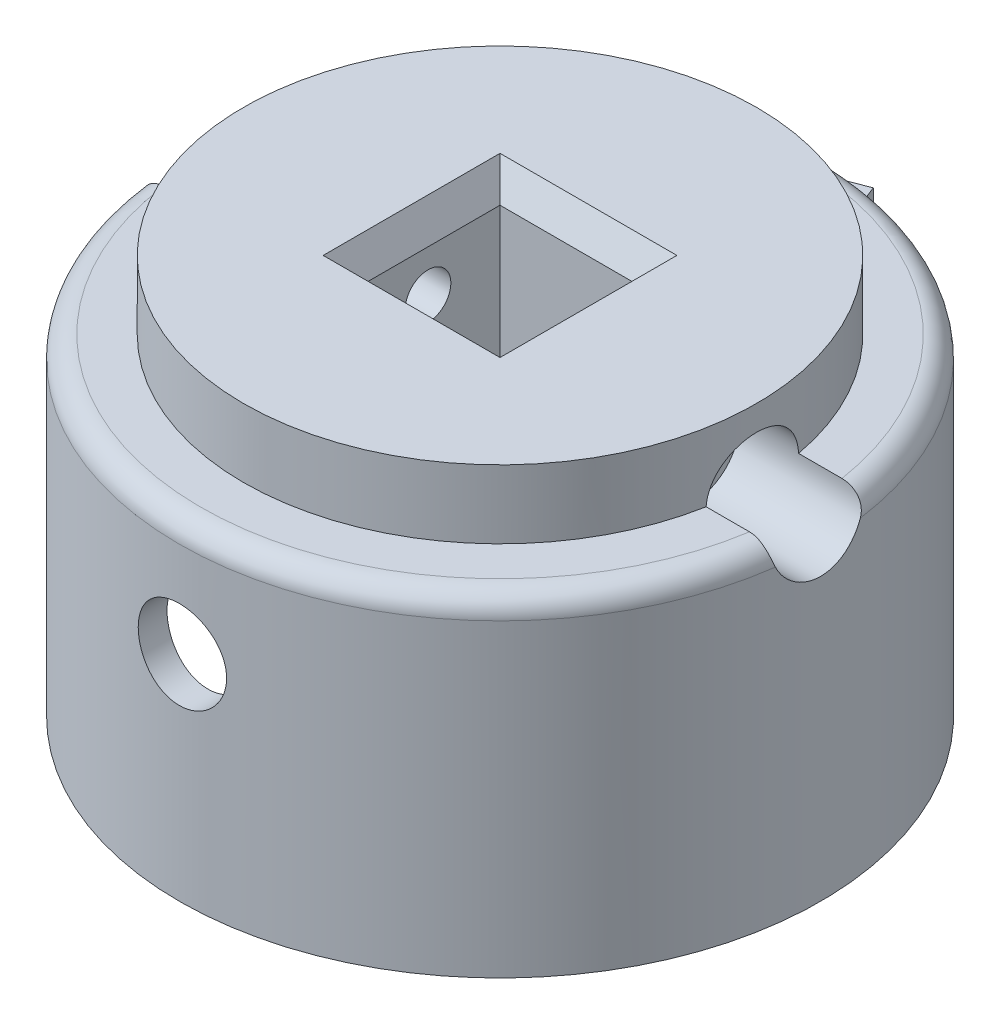
SolidWorks part; units mm, degrees
ref_plane "Спереди" through (0, 0, 0) normal (0, 0, 1) x (1, 0, 0)
ref_plane "Сверху" through (0, 0, 0) normal (0, 1, 0) x (1, 0, 0)
ref_plane "Справа" through (0, 0, 0) normal (1, 0, 0) x (0, 0, -1)
sketch "Sketch1" plane through (0, 0, 0) normal (0, 1, 0) x (1, 0, 0)
  circle A0 centre (0, 0) radius 22.5
  dimension "D1" = 45
extrude "Boss-Extrude1" add sketch "Sketch1" along normal blind 28
sketch "Sketch2" plane through (0, 0, 0) normal (0, -1, 0) x (1, 0, 0)
  line L1 (5.05, 5.05) -> (-5.05, 5.05)
  line L2 (5.05, 5.05) -> (5.05, -5.05)
  line L3 (5.05, -5.05) -> (-5.05, -5.05)
  line L4 (-5.05, 5.05) -> (-5.05, -5.05)
  line L5 (5.05, 5.05) -> (-5.05, -5.05) construction
  line L6 (5.05, -5.05) -> (-5.05, 5.05) construction
  point P0 (0, 0)
  dimension "D1" = 10.1
extrude "Cut-Extrude2" cut sketch "Sketch2" against normal through all
shell "Shell3" thickness 2 removed face at (0, 0, 0)
sketch "Sketch3" plane through (0, 0, 7.05) normal (0, 0, 1) x (1, 0, 0)
  line L0 (0, 26) -> (0, 0) construction
  line L1 (7.05, 26) -> (-7.05, 26) construction
  line L2 (7.05, 0) -> (-7.05, 0) construction
  line L3 (-22.5, 0) -> (22.5, 0) construction
  circle A0 centre (0, 15) radius 3.1
  dimension "D1" = 6.2
  dimension "D2" = 15
extrude "Cut-Extrude3" cut sketch "Sketch3" along normal through all
chamfer "Chamfer1" distance 2 angle 30 4 edges at (-5.05, 28, 0) (0, 28, 5.05) (5.05, 28, 0) (0, 28, -5.05) first distance on face at (-5.05, 14, 0) first distance on face at (0, 14, 5.05) first distance on face at (5.05, 14, 0) first distance on face at (0, 14, -5.05)
sketch "Sketch18" plane through (0, 26, 0) normal (0, -1, 0) x (1, 0, 0)
  line L0 (0, 0) -> (-18.4253, -8.9866) construction
  line L1 (0, 0) -> (-17.385, 10.8633) construction
  line L2 (0, 0) -> (0, -20.5) construction
  line L3 (-15.7289, -7.6715) -> (-18.4253, -8.9866)
  line L4 (-14.8408, 9.2736) -> (-17.385, 10.8633)
  circle A0 centre (0, 0) radius 20.5 construction
  arc A1 (-18.4253, -8.9866) -> (-17.385, 10.8633) centre (0, 0) cw
  arc A2 (-14.8408, 9.2736) -> (-15.7289, -7.6715) centre (0, 0) ccw
  dimension "D1" = 64
  dimension "D2" = 58
  dimension "D3" = 3
extrude "Boss-Extrude8" add sketch "Sketch18" along normal offset from surface (23 mm away) 3 up to face at (0, 0, 20.5)
sketch "Sketch9" plane through (0, 0, 0) normal (0, -1, 0) x (1, 0, 0)
  line L0 (0, -7.05) -> (0, -20.5) construction
  line L2 (2.0704, -22.4045) -> (-16.5877, -15.202)
  line L3 (-16.5877, -15.202) -> (-17.6681, -18.0007)
  line L4 (-17.6681, -18.0007) -> (0.99, -25.2032)
  line L5 (0.99, -25.2032) -> (2.0704, -22.4045)
  line L6 (-7.05, -7.05) -> (7.05, -7.05) construction
  line L7 (2.0704, -22.4045) -> (0, -7.05) construction
  circle A0 centre (0, 0) radius 22.5 construction
  circle A1 centre (0, 0) radius 20.5 construction
  dimension "D1" = 20
  dimension "D2" = 3
  dimension "D3" = 7.679
extrude "Boss-Extrude4" add sketch "Sketch9" against normal blind 20
sketch "Sketch11" plane through (0, 0, 0) normal (0, -1, 0) x (1, 0, 0)
  line L0 (2.0704, -22.4045) -> (7.05, -7.05)
  line L1 (7.05, -7.05) -> (-7.05, -7.05)
  line L2 (-7.05, -7.05) -> (-16.5877, -15.202)
  line L3 (-16.5877, -15.202) -> (2.0704, -22.4045) construction
  line L4 (-3.768, -20.1507) -> (-10.7492, -17.4558) construction
  arc A0 (2.0704, -22.4045) -> (-16.5877, -15.202) centre (0, 0) ccw construction
  arc A1 (2.0704, -22.4045) -> (-16.5877, -15.202) centre (0, 0) cw
  arc A2 (2.0704, -22.4045) -> (-16.5877, -15.202) centre (0, 0) ccw construction
  point P4 (-7.2586, -18.8032)
extrude "Boss-Extrude6" add sketch "Sketch11" against normal up to surface (26 mm away) up to face at (0, 26, 0)
sketch "Sketch12" plane through (0, 0, 0) normal (0, -1, 0) x (1, 0, 0)
  line L0 (-7.05, -7.05) -> (-15.0663, -13.9016) construction
  line L1 (2.748, -20.315) -> (7.05, -7.05) construction
  line L2 (3.7952, -17.0861) -> (2.748, -20.315)
  line L3 (-15.0663, -13.9016) -> (-12.7858, -11.9525)
  arc A0 (2.748, -20.315) -> (-15.0663, -13.9016) centre (0, 0) cw
  arc A1 (-12.7858, -11.9525) -> (3.7952, -17.0861) centre (0, 0) ccw
  arc A2 (2.748, -20.315) -> (-15.0663, -13.9016) centre (0, 0) ccw construction
  dimension "D1" = 3
extrude "Cut-Extrude5" cut sketch "Sketch12" against normal blind 12
sketch "Sketch13" plane through (-8.339, 0, -21.602) normal (-0.3601, 0, -0.9329) x (-0.9329, 0, 0.3601)
  line L0 (0, 20) -> (0, 0) construction
  line L1 (10, 20) -> (-10, 20) construction
  line L2 (10, 0) -> (-10, 0) construction
  circle A0 centre (0, 10) radius 3.8
  dimension "D1" = 7.6
extrude "Cut-Extrude6" cut sketch "Sketch13" against normal blind 16
sketch "Sketch15" plane through (-8.339, 0, -21.602) normal (-0.3601, 0, -0.9329) x (-0.9329, 0, 0.3601)
  line L0 (-10, 10) -> (10, 10) construction
  line L1 (-10, 20) -> (-10, 0) construction
  line L2 (10, 20) -> (10, 0) construction
  line L4 (5, 11.5) -> (-5, 11.5)
  line L5 (5, 11.5) -> (5, 8.5)
  line L6 (5, 8.5) -> (-5, 8.5)
  line L7 (-5, 11.5) -> (-5, 8.5)
  line L8 (5, 11.5) -> (-5, 8.5) construction
  line L9 (5, 8.5) -> (-5, 11.5) construction
  point P6 (0, 10)
  dimension "D1" = 10
  dimension "D2" = 3
extrude "Cut-Extrude8" cut sketch "Sketch15" against normal blind 16
sketch "Sketch17" plane through (0, 0, 0) normal (0, -1, 0) x (1, 0, 0)
  line L0 (7.05, 7.05) -> (7.05, -7.05)
  line L1 (7.05, -7.05) -> (3.7952, -17.0861)
  line L2 (7.05, 7.05) -> (-7.05, 7.05)
  line L3 (-7.05, 7.05) -> (-7.05, -7.05)
  line L4 (-7.05, -7.05) -> (-12.7858, -11.9525)
  arc A0 (3.7952, -17.0861) -> (-12.7858, -11.9525) centre (0, 0) cw
  arc A1 (-12.7858, -11.9525) -> (3.7952, -17.0861) centre (0, 0) ccw construction
extrude "Cut-Extrude9" cut sketch "Sketch17" against normal blind 2
sketch "Sketch20" plane through (0, 26, 0) normal (0, -1, 0) x (1, 0, 0)
  line L0 (2.748, -20.315) -> (7.05, -7.05)
  line L1 (7.05, -7.05) -> (7.05, 7.05)
  line L2 (7.05, 7.05) -> (-7.05, 7.05)
  line L3 (-7.05, 7.05) -> (-7.05, -7.05)
  line L4 (-7.05, -7.05) -> (-15.0663, -13.9016)
  arc A0 (2.748, -20.315) -> (-15.0663, -13.9016) centre (0, 0) ccw
  arc A1 (2.748, -20.315) -> (-17.385, 10.8633) centre (0, 0) ccw construction
extrude "Boss-Extrude10" add sketch "Sketch20" along normal blind 7
sketch "Sketch21" plane through (0, 28, 0) normal (0, 1, 0) x (1, 0, 0)
  circle A0 centre (0, 0) radius 18
  dimension "D1" = 36
extrude "Cut-Extrude11" cut sketch "Sketch21" against normal blind 4.8 flip side to cut
sketch "Sketch22" plane through (5.05, 0, 0) normal (-1, 0, 0) x (0, 0, 1)
  line L0 (0, 26) -> (0, 2) construction
  line L1 (5.05, 26) -> (-5.05, 26) construction
  line L2 (-5.05, 2) -> (5.05, 2) construction
  line L3 (-6.2047, 28) -> (6.2047, 28) construction
  circle A0 centre (0, 23) radius 1.6
  point P10 (0, 28)
  dimension "D1" = 3.2
  dimension "D2" = 5
extrude "Cut-Extrude12" cut sketch "Sketch22" against normal through all both and the other way through all
sketch "Sketch24" plane through (5.05, 0, 0) normal (-1, 0, 0) x (0, 0, 1)
  circle A0 centre (0, 23) radius 3.25
  dimension "D1" = 6.5
extrude "Cut-Extrude13" cut sketch "Sketch24" against normal through all from offset 8.5 offset against normal yes
sketch "Sketch25" plane through (-5.05, 0, 0) normal (1, 0, 0) x (0, 0, -1)
  line L0 (-5.05, 26) -> (-5.05, 2) construction
  line L1 (0, 19.75) -> (2.8146, 21.375)
  line L2 (2.8146, 21.375) -> (2.8146, 24.625)
  line L3 (2.8146, 24.625) -> (0, 26.25)
  line L4 (0, 26.25) -> (-2.8146, 24.625)
  line L5 (-2.8146, 24.625) -> (-2.8146, 21.375)
  line L6 (-2.8146, 21.375) -> (0, 19.75)
  circle A0 centre (0, 23) radius 3.25 construction
  dimension "D1" = 6.5
extrude "Cut-Extrude14" cut sketch "Sketch25" against normal through all from offset 8.5 offset against normal yes
fillet "Fillet1" radius 1.5 2 edges at (-0.2166, 23.2, 22.499) (-0.2166, 23.2, -22.499)
chamfer "Chamfer2" distance 0.5 angle 70 4 edges at (0, 2, 5.05) (-5.05, 2, 0) (0, 2, -5.05) (5.05, 2, 0) first distance on face at (-1.612, 2, -5.2065)
